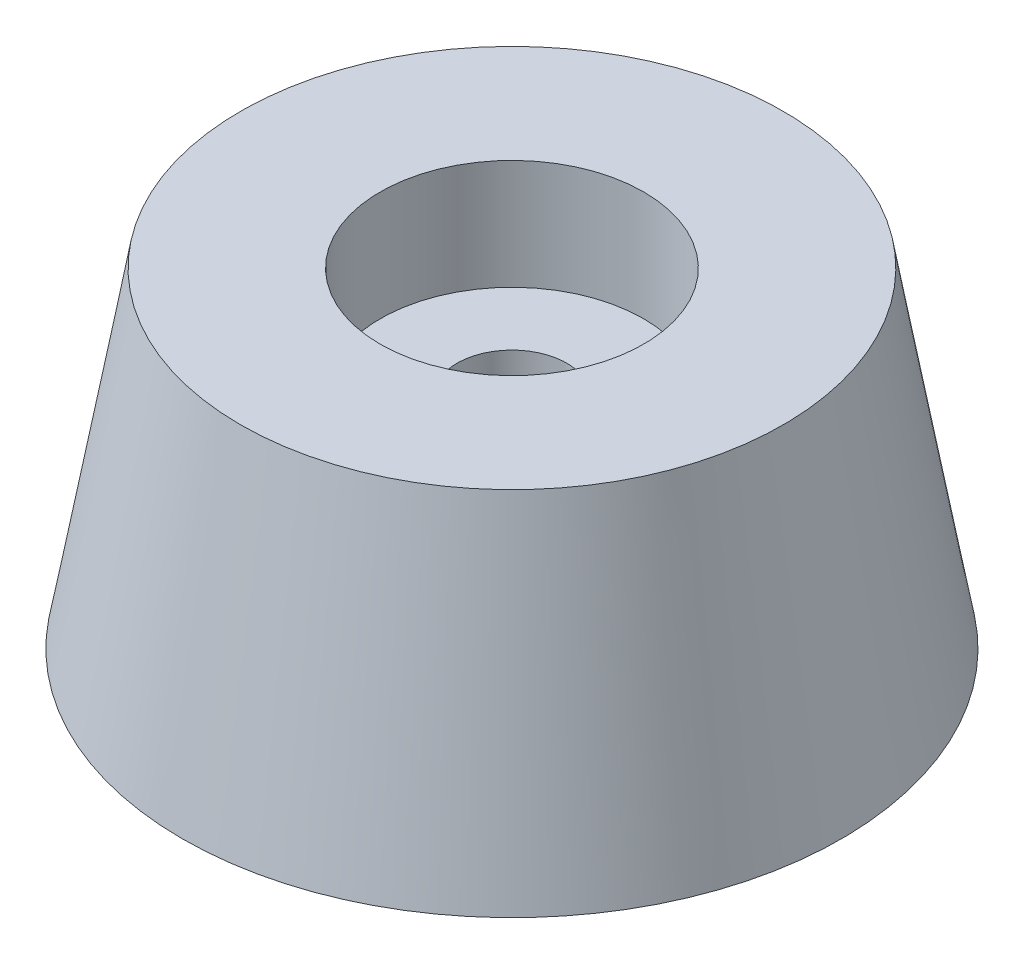
SolidWorks part; units mm, degrees
ref_plane "Front Plane" through (0, 0, 0) normal (0, 0, 1) x (1, 0, 0)
ref_plane "Top Plane" through (0, 0, 0) normal (0, 1, 0) x (1, 0, 0)
ref_plane "Right Plane" through (0, 0, 0) normal (1, 0, 0) x (0, 0, -1)
sketch "Sketch1" plane through (0, 0, 0) normal (0, 1, 0) x (1, 0, 0)
  circle A0 centre (0, 0) radius 15
  dimension "D1" = 30
extrude "Boss-Extrude1" add sketch "Sketch1" along normal blind 15 draft 10
sketch "Sketch2" plane through (0, 15, 0) normal (0, 1, 0) x (1, 0, 0)
  circle A0 centre (0, 0) radius 6
  dimension "D1" = 12
extrude "Cut-Extrude1" cut sketch "Sketch2" against normal blind 5
sketch "Sketch3" plane through (0, 10, 0) normal (0, 1, 0) x (1, 0, 0)
  circle A0 centre (0, 0) radius 2.5
  dimension "D1" = 5
extrude "Cut-Extrude2" cut sketch "Sketch3" against normal through all
